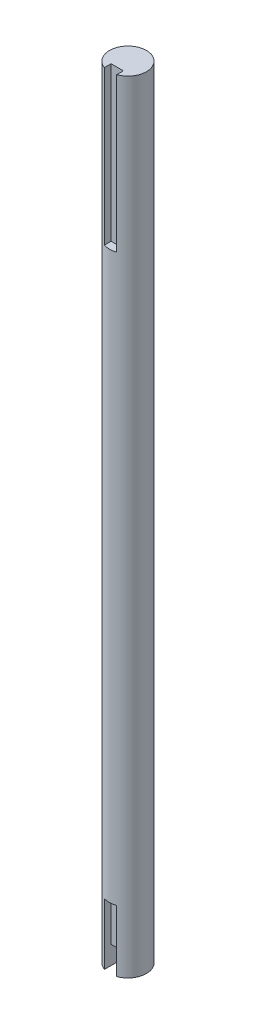
SolidWorks part; units mm, degrees
ref_plane "Front Plane" through (0, 0, 0) normal (0, 0, 1) x (1, 0, 0)
ref_plane "Top Plane" through (0, 0, 0) normal (0, 1, 0) x (1, 0, 0)
ref_plane "Right Plane" through (0, 0, 0) normal (1, 0, 0) x (0, 0, -1)
sketch "Sketch1" plane through (0, 0, 0) normal (0, 1, 0) x (1, 0, 0)
  circle A0 centre (0, 0) radius 6
  dimension "D1" = 12
extrude "Boss-Extrude1" add sketch "Sketch1" along normal blind 254
sketch "Sketch2" plane through (0, 0, 0) normal (0, 1, 0) x (1, 0, 0)
  line L1 (-2, -8.5) -> (2, -8.5)
  line L2 (-2, -8.5) -> (-2, -3.5)
  line L3 (-2, -3.5) -> (2, -3.5)
  line L4 (2, -8.5) -> (2, -3.5)
  line L5 (-2, -8.5) -> (2, -3.5) construction
  line L6 (-2, -3.5) -> (2, -8.5) construction
  circle A0 centre (0, 0) radius 6 construction
  point P0 (0, -6)
  dimension "D1" = 2.5
  dimension "D2" = 4
extrude "Cut-Extrude3" cut sketch "Sketch2" against normal blind 0.0001 and the other way blind 20
extrude "Cut-Extrude4" cut sketch "Sketch2<2>" against normal blind 50 from surface starting at face at (0, 254, 6)
sketch "Sketch2<2>" plane through (0, 0, 0) normal (0, 1, 0) x (1, 0, 0) same geometry as "Sketch2"
sketch "Sketch3" plane through (0, 0, 0) normal (0, 1, 0) x (1, 0, 0)
  line L1 (-2, -11) -> (2, -11)
  line L2 (-2, -11) -> (-2, -1)
  line L3 (-2, -1) -> (2, -1)
  line L4 (2, -11) -> (2, -1)
  line L5 (-2, -11) -> (2, -1) construction
  line L6 (-2, -1) -> (2, -11) construction
  arc A0 (-2, -5.6569) -> (2, -5.6569) centre (0, 0) ccw construction
  point P0 (0, -6)
  dimension "D1" = 4
  dimension "D2" = 5
extrude "Cut-Extrude6" cut sketch "Sketch3" along normal blind 6
